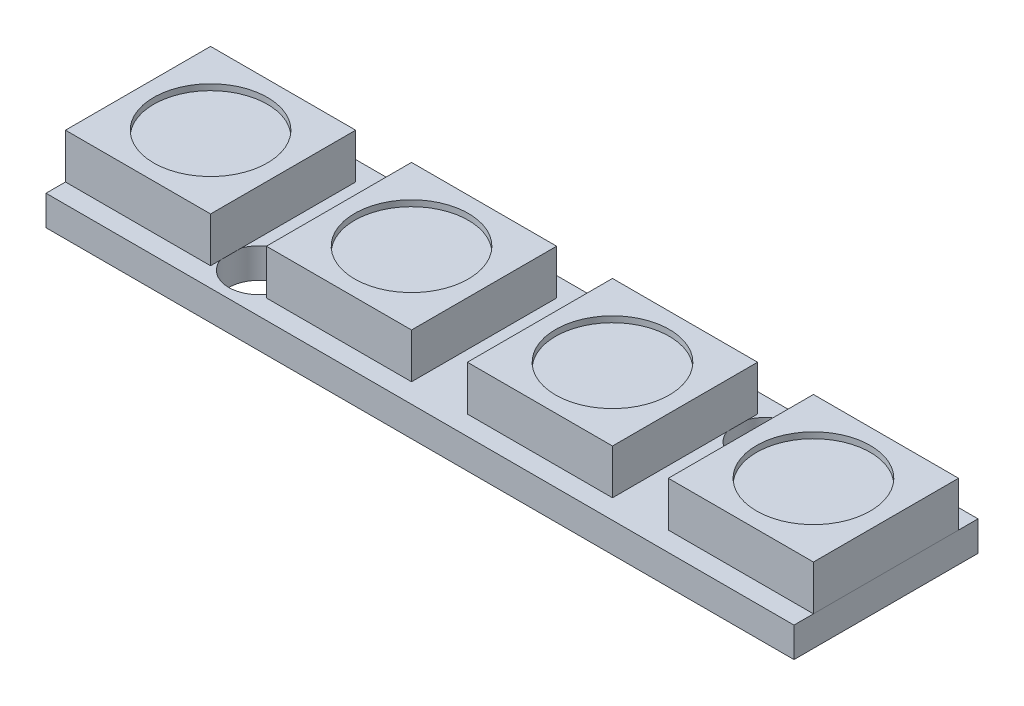
SolidWorks part; units mm, degrees
ref_plane "Front Plane" through (0, 0, 0) normal (0, 0, 1) x (1, 0, 0)
ref_plane "Top Plane" through (0, 0, 0) normal (0, 1, 0) x (1, 0, 0)
ref_plane "Right Plane" through (0, 0, 0) normal (1, 0, 0) x (0, 0, -1)
sketch "Sketch1" plane through (0, 0, 0) normal (0, 1, 0) x (1, 0, 0)
  line L1 (-12.5, 3.075) -> (12.5, 3.075)
  line L2 (-12.5, 3.075) -> (-12.5, -3.075)
  line L3 (-12.5, -3.075) -> (12.5, -3.075)
  line L4 (12.5, 3.075) -> (12.5, -3.075)
  line L5 (-12.5, 3.075) -> (12.5, -3.075) construction
  line L6 (-12.5, -3.075) -> (12.5, 3.075) construction
  point P0 (0, 0)
  dimension "D1" = 25
  dimension "D2" = 6.15
extrude "Boss-Extrude1" add sketch "Sketch1" along normal blind 1
sketch "Sketch2" plane through (0, 1, 0) normal (0, 1, 0) x (1, 0, 0)
  line L0 (-12.5, 0) -> (12.5, 0) construction
  line L1 (-12.5, 3.075) -> (-12.5, -3.075) construction
  line L2 (12.5, -3.075) -> (12.5, 3.075) construction
  line L3 (0, 3.075) -> (0, -3.075) construction
  line L4 (12.5, 3.075) -> (-12.5, 3.075) construction
  line L5 (-12.5, -3.075) -> (12.5, -3.075) construction
  line L6 (-0.9333, 2.425) -> (-0.9333, -2.425)
  line L7 (-12.5, 2.425) -> (-7.65, 2.425)
  line L8 (-12.5, 2.425) -> (-12.5, -2.425)
  line L9 (-12.5, -2.425) -> (-7.65, -2.425)
  line L10 (-7.65, 2.425) -> (-7.65, -2.425)
  line L11 (-12.5, 2.425) -> (-7.65, -2.425) construction
  line L12 (-12.5, -2.425) -> (-7.65, 2.425) construction
  line L13 (-5.7833, -2.425) -> (-0.9333, -2.425)
  line L14 (-5.7833, 2.425) -> (-5.7833, -2.425)
  line L15 (-5.7833, 2.425) -> (-0.9333, 2.425)
  line L16 (5.7833, 2.425) -> (5.7833, -2.425)
  line L17 (0.9333, -2.425) -> (5.7833, -2.425)
  line L18 (0.9333, 2.425) -> (0.9333, -2.425)
  line L19 (0.9333, 2.425) -> (5.7833, 2.425)
  line L20 (12.5, 2.425) -> (12.5, -2.425)
  line L21 (7.65, -2.425) -> (12.5, -2.425)
  line L22 (7.65, 2.425) -> (7.65, -2.425)
  line L23 (7.65, 2.425) -> (12.5, 2.425)
  point P12 (-10.075, 0)
  dimension "D1" = 4.85
  dimension "D2" = 4
extrude "Boss-Extrude2" add sketch "Sketch2" along normal blind 1.5 separate body
sketch "Sketch3" plane through (0, 1, 0) normal (0, 1, 0) x (1, 0, 0)
  line L0 (-7.65, 0) -> (-5.7833, 0) construction
  line L1 (-7.65, -2.425) -> (-7.65, 2.425) construction
  line L3 (-6.7167, 0) -> (-6.7167, -3.075) construction
  line L4 (-12.5, -3.075) -> (12.5, -3.075) construction
  line L5 (0, 1.5648) -> (0, -1.0518) construction
  line L7 (-2.2575, 0) -> (3.2836, 0) construction
  line L8 (-5.7833, 2.425) -> (-5.7833, -2.425) construction
  circle A0 centre (-6.7167, -1.75) radius 1
  circle A1 centre (6.7167, -1.75) radius 1
  circle A2 centre (6.7167, 1.75) radius 1
  point P4 (0, 0)
  dimension "D1" = 2
  dimension "D2" = 3.5
extrude "Cut-Extrude1" cut sketch "Sketch3" against normal up to next (1 mm away) contours A0 | A2
sketch "Sketch4" plane through (0, 2.5, 0) normal (0, 1, 0) x (1, 0, 0)
  line L0 (-12.5, 2.425) -> (-7.65, -2.425) construction
  line L1 (-5.7833, 2.425) -> (-0.9333, -2.425) construction
  line L2 (0.9333, 2.425) -> (5.7833, -2.425) construction
  line L3 (7.65, 2.425) -> (12.5, -2.425) construction
  line L4 (-0.9333, 2.425) -> (-5.7833, 2.425) construction
  line L5 (-5.7833, 2.425) -> (-5.7833, -2.425) construction
  line L6 (12.5, -2.425) -> (12.5, 2.425) construction
  circle A0 centre (-10.075, 0) radius 1.9
  circle A1 centre (-3.3583, 0) radius 1.9
  circle A2 centre (3.3583, 0) radius 1.9
  circle A3 centre (10.075, 0) radius 1.9
  point P24 (-12.5, 2.425)
  point P26 (-7.65, -2.425)
  point P28 (-5.7833, 2.425)
  point P31 (-0.9333, -2.425)
  point P33 (-5.7833, 2.425)
  point P36 (0.9333, 2.425)
  point P38 (5.7833, -2.425)
  point P40 (12.5, -2.425)
  point P43 (7.65, 2.425)
  point P44 (12.5, -2.425)
  dimension "D1" = 3.8
extrude "Cut-Extrude2" cut sketch "Sketch4" against normal blind 0.2
sketch "Sketch5" plane through (0, 0, 0) normal (0, -1, 0) x (1, 0, 0)
  line L0 (-12.5, 1.475) -> (12.5, 1.475) construction
  line L1 (-12.5, -3.075) -> (-12.5, 3.075) construction
  line L2 (12.5, 3.075) -> (12.5, -3.075) construction
  line L3 (0, 3.075) -> (0, -3.075) construction
  line L4 (-12.5, 3.075) -> (12.5, 3.075) construction
  line L5 (12.5, -3.075) -> (-12.5, -3.075) construction
  circle A0 centre (0, 1.475) radius 0.8
  circle A1 centre (2.54, 1.475) radius 0.8
  circle A2 centre (-2.54, 1.475) radius 0.8
  dimension "D2" = 1.6
  dimension "D1" = 1.6
  dimension "D4" = 2.54
  dimension "D3" = 2
extrude "Cut-Extrude3" cut sketch "Sketch5" against normal blind 0.01
